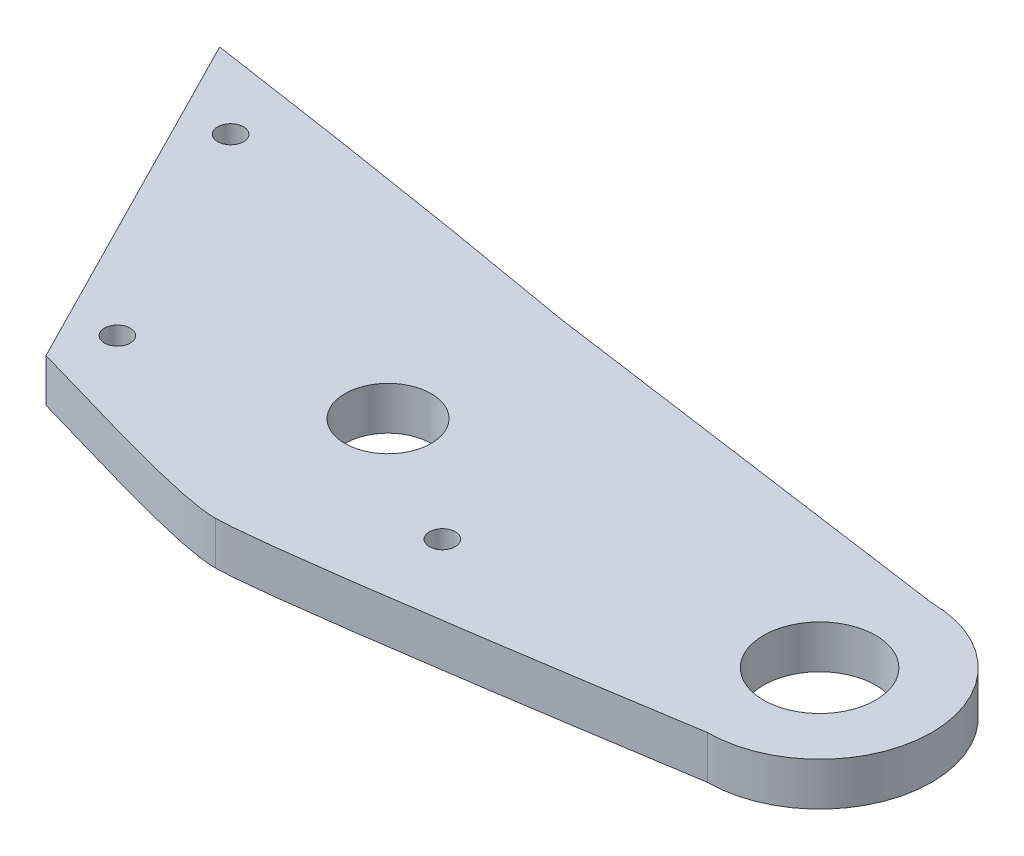
SolidWorks part; units mm, degrees
ref_plane "Front Plane" through (0, 0, 0) normal (0, 0, 1) x (1, 0, 0)
ref_plane "Top Plane" through (0, 0, 0) normal (0, 1, 0) x (1, 0, 0)
ref_plane "Right Plane" through (0, 0, 0) normal (1, 0, 0) x (0, 0, -1)
sketch "Sketch1" plane through (0, 0, 0) normal (0, 1, 0) x (1, 0, 0)
  line L0 (0, 0) -> (-300, 0) construction
  line L1 (0, 0) -> (50, 0) construction
  line L2 (-300, 0) -> (-300, 40) construction
  line L3 (-328.2843, 28.2843) -> (-271.7157, -28.2843) construction
  circle A0 centre (0, 0) radius 5
  circle A1 centre (50, 0) radius 6.5
  circle A2 centre (-300, 0) radius 40
  circle A3 centre (0, 0) radius 20
  circle A4 centre (50, 0) radius 13
  spline S0 degree 3 poles (-271.7157, -28.2843) (-189.2199, 54.2115) (-20, -20) (0, -20) knots 0 0 0 0 1 1 1 1
  spline S1 degree 3 poles (-328.2843, 28.2843) (-300, 56.5685) (-114.8731, 40.3783) (0, 20) knots 0 0 0 0 1 1 1 1
  spline S2 degree 2 poles (0, -20) (5.9085, -20) (50, -13) knots 0 0 0 1 1 1
  spline S3 degree 2 poles (0, 20) (0.0315, 20) (50, 13) knots 0 0 0 1 1 1
  dimension "D3" = 10
  dimension "D4" = 13
  dimension "D5" = 80
  dimension "D6" = 40
  dimension "D7" = 45
  dimension "D8" = 120
  dimension "D9" = 350
  dimension "D10" = 350
  dimension "D11" = 60
  dimension "D12" = 26
  dimension "D1" = 50
  dimension "D2" = 300
extrude "Boss-Extrude1" add sketch "Sketch1" along normal blind 20 and the other way blind 20 contours S1 A2 | S1 A2 S0 A3 | S3 A3 S0 A0 | S3 A3 S2 A4 | A4 A1 region at (-299.9271, 0, 0.2395) region at (-151.7179, 0, -19.1123) region at (-19.1932, 0, -3.0516) region at (27.8762, 0, 0.2883) region at (58.9324, 0, -8.9324)
ref_plane "Plane2" through (0, 20, 0) normal (0, 1, 0) x (1, 0, 0)
sketch "Sketch5" plane through (0, 20, 0) normal (0, 1, 0) x (1, 0, 0)
  line L0 (-47.037, 27.5275) -> (92.1208, 16.1646)
  line L1 (92.1208, 16.1646) -> (85.7247, -16.9188)
  line L2 (85.7247, -16.9188) -> (-17.2628, -30.9078)
  line L3 (-17.2628, -30.9078) -> (-47.037, 27.5275)
  line L4 (0, 0) -> (0, 89.1393) construction
  spline S0 degree 3 poles (-328.2843, 28.2843) (-300, 56.5685) (-114.8731, 40.3783) (0, 20) knots 0 0 0 0 1 1 1 1 construction
  dimension "D1" = 27
  dimension "D2" = 54.5
extrude "Cut-Extrude4" cut sketch "Sketch5" against normal blind 35
sketch "Sketch6" plane through (0, -20, 0) normal (0, -1, 0) x (-1, 0, 0)
  circle A1 centre (24.0052, -7.3569) radius 1.5
  circle A2 centre (-15.2511, -8.9603) radius 1.5
  circle A3 centre (37.6431, 19.409) radius 1.5
  dimension "D1" = 3
extrude "Cut-Extrude5" cut sketch "Sketch6" against normal blind 10
sketch "Sketch7" plane through (0, 20, 0) normal (0, 1, 0) x (1, 0, 0)
  line L0 (-47.037, 27.5275) -> (-26.1377, -13.4898)
  line L1 (-26.1377, -13.4898) -> (-379.5957, -92.5802)
  line L2 (-379.5957, -92.5802) -> (-321.5056, 137.2547)
  line L3 (-321.5056, 137.2547) -> (-47.037, 27.5275)
extrude "Cut-Extrude6" cut sketch "Sketch7" against normal blind 50
